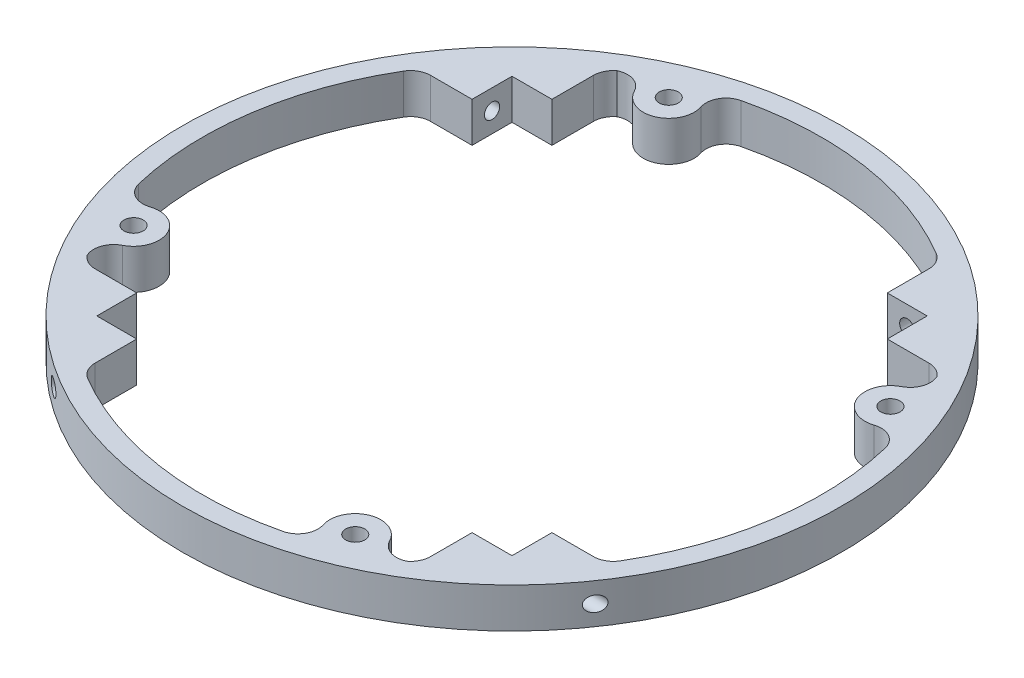
SolidWorks part; units mm, degrees
material "6061-T6 (SS)"
ref_plane "Front Plane" through (0, 0, 0) normal (0, 0, 1) x (1, 0, 0)
ref_plane "Top Plane" through (0, 0, 0) normal (0, 1, 0) x (1, 0, 0)
ref_plane "Right Plane" through (0, 0, 0) normal (1, 0, 0) x (0, 0, -1)
sketch "Sketch1" plane through (0, 0, 0) normal (0, 1, 0) x (1, 0, 0)
  line L0 (0, 0) -> (0, 84.2831) construction
  line L1 (-52, 52) -> (52, 52) construction
  line L2 (-52, 52) -> (-52, -52) construction
  line L3 (-52, -52) -> (52, -52) construction
  line L4 (52, 52) -> (52, -52) construction
  line L5 (0, 0) -> (-99.9306, 0) construction
  line L6 (0, 0) -> (-52, 52) construction
  line L7 (0, 0) -> (-31.8699, 76.9407) construction
  line L8 (-42, 52) -> (-52, 52)
  line L9 (-52, 52) -> (-52, 42)
  line L10 (-52, 42) -> (-65.192, 42)
  line L11 (-42, 52) -> (-42, 65.192)
  line L12 (-35.4887, 68.9533) -> (-33.6765, 64.5783)
  line L13 (-23.663, 73.8516) -> (-21.8509, 69.4766)
  line L14 (42, 52) -> (42, 65.192)
  line L15 (52, 52) -> (42, 52)
  line L16 (52, 42) -> (52, 52)
  line L17 (52, 42) -> (65.192, 42)
  line L18 (68.9533, 35.4887) -> (64.5783, 33.6765)
  line L19 (73.8516, 23.663) -> (69.4766, 21.8509)
  line L20 (52, -42) -> (65.192, -42)
  line L21 (52, -52) -> (52, -42)
  line L22 (42, -52) -> (52, -52)
  line L23 (42, -52) -> (42, -65.192)
  line L24 (35.4887, -68.9533) -> (33.6765, -64.5783)
  line L25 (23.663, -73.8516) -> (21.8509, -69.4766)
  line L26 (-42, -52) -> (-42, -65.192)
  line L27 (-52, -52) -> (-42, -52)
  line L28 (-52, -42) -> (-52, -52)
  line L29 (-52, -42) -> (-65.192, -42)
  line L30 (-68.9533, -35.4887) -> (-64.5783, -33.6765)
  line L31 (-73.8516, -23.663) -> (-69.4766, -21.8509)
  circle A0 centre (0, 0) radius 82.55
  arc A1 (-65.192, 42) -> (-77.55, 0) centre (0, 0) ccw
  arc A2 (-42, 65.192) -> (-35.4887, 68.9533) centre (0, 0) cw
  arc A3 (-33.6765, 64.5783) -> (-21.8509, 69.4766) centre (-27.7637, 67.0275) ccw
  arc A4 (0, 77.55) -> (-23.663, 73.8516) centre (0, 0) ccw
  arc A5 (42, 65.192) -> (0, 77.55) centre (0, 0) ccw
  arc A6 (65.192, 42) -> (68.9533, 35.4887) centre (0, 0) cw
  arc A7 (64.5783, 33.6765) -> (69.4766, 21.8509) centre (67.0275, 27.7637) ccw
  arc A8 (77.55, 0) -> (73.8516, 23.663) centre (0, 0) ccw
  arc A9 (65.192, -42) -> (77.55, 0) centre (0, 0) ccw
  arc A10 (42, -65.192) -> (35.4887, -68.9533) centre (0, 0) cw
  arc A11 (33.6765, -64.5783) -> (21.8509, -69.4766) centre (27.7637, -67.0275) ccw
  arc A12 (0, -77.55) -> (23.663, -73.8516) centre (0, 0) ccw
  arc A13 (-42, -65.192) -> (0, -77.55) centre (0, 0) ccw
  arc A14 (-65.192, -42) -> (-68.9533, -35.4887) centre (0, 0) cw
  arc A15 (-64.5783, -33.6765) -> (-69.4766, -21.8509) centre (-67.0275, -27.7637) ccw
  arc A16 (-77.55, 0) -> (-73.8516, -23.663) centre (0, 0) ccw
  point P21 (-22.7569, 71.6641)
  point P61 (0, 0)
  dimension "D1" = 165.1
  dimension "D2" = 104
  dimension "D3" = 22.5
  dimension "D4" = 5
  dimension "D5" = 72.55
  dimension "D6" = 12.8
  dimension "D7" = 10
  dimension "D8" = 4
extrude "Boss-Extrude1" add sketch "Sketch1" along normal blind 10
fillet "Fillet1" radius 5 16 edges at (-73.8516, 5, 23.663) (-68.9533, 5, 35.4887) (-42, 5, 65.192) (-65.192, 5, 42) (23.663, 5, 73.8516) (35.4887, 5, 68.9533) (42, 5, 65.192) (65.192, 5, 42) (73.8516, 5, -23.663) (68.9533, 5, -35.4887) (65.192, 5, -42) (42, 5, -65.192) (-35.4887, 5, -68.9533) (-23.663, 5, -73.8516) (-42, 5, -65.192) (-65.192, 5, -42)
hole_wizard "#12 (0.189) Diameter Hole1" positions "Sketch4" profile "Sketch3" hole size "#12" standard "ANSI Inch" end condition through all
sketch "Sketch4" plane through (0, 10, 0) normal (0, 1, 0) x (1, 0, 0)
  point P0 (67.0275, 27.7637)
sketch "Sketch3" plane through (67.0275, 10, -27.7637) normal (1, 0, 0) x (0, 0, 1)
  line L0 (0, 0) -> (0, 10)
  line L1 (0, 10) -> (2.4003, 10)
  line L2 (2.4003, 10) -> (2.4003, 0)
  line L5 (2.4003, 0) -> (0, 0)
  line L11 (0, -6.35) -> (0, 107.95) construction
  dimension "Thru Hole Dia." = 4.8006
  dimension "Thru Hole Depth" = 10
hole_wizard "#10-24 Tapped Hole1" positions "Sketch8" profile "Sketch9" tap size "#10-24" standard "ANSI Inch" end condition through all
sketch "Sketch8" plane through (0, 0, -52) normal (0, 0, 1) x (1, 0, 0)
  line L0 (52, 0) -> (42, 10)
  point P0 (47, 5)
  point P10 (47, 5)
sketch "Sketch9" plane through (47, 5, -52) normal (1, 0, 0) x (0, -1, 0)
  line L0 (0, 0) -> (0, 30.55)
  line L1 (0, 30.55) -> (1.8986, 30.55)
  line L2 (1.8986, 30.55) -> (1.8986, 0)
  line L5 (1.8986, 0) -> (0, 0)
  line L11 (0, -6.35) -> (0, 107.95) construction
  dimension "Thru Tap Drill Dia." = 3.7973
  dimension "Thru Tap Drill Depth" = 30.55
cosmetic thread "Hole Thread2" parameters "D2"=4.826
ref_axis "Axis1" through (0, 10.5, 0) along (0, -1, 0)
pattern_circular "CirPattern1" count 4 over 360 about axis through (0, 10.5, 0) along (0, -1, 0) of "#12 (0.189) Diameter Hole1", "#10-24 Tapped Hole1"
equation "\"TubeDiameter\" = 6.500in"
equation "\"D1@Sketch1\"=\"TubeDiameter\""
equation "\"D5@Sketch1\"=\"TubeDiameter\"/2-10mm"
